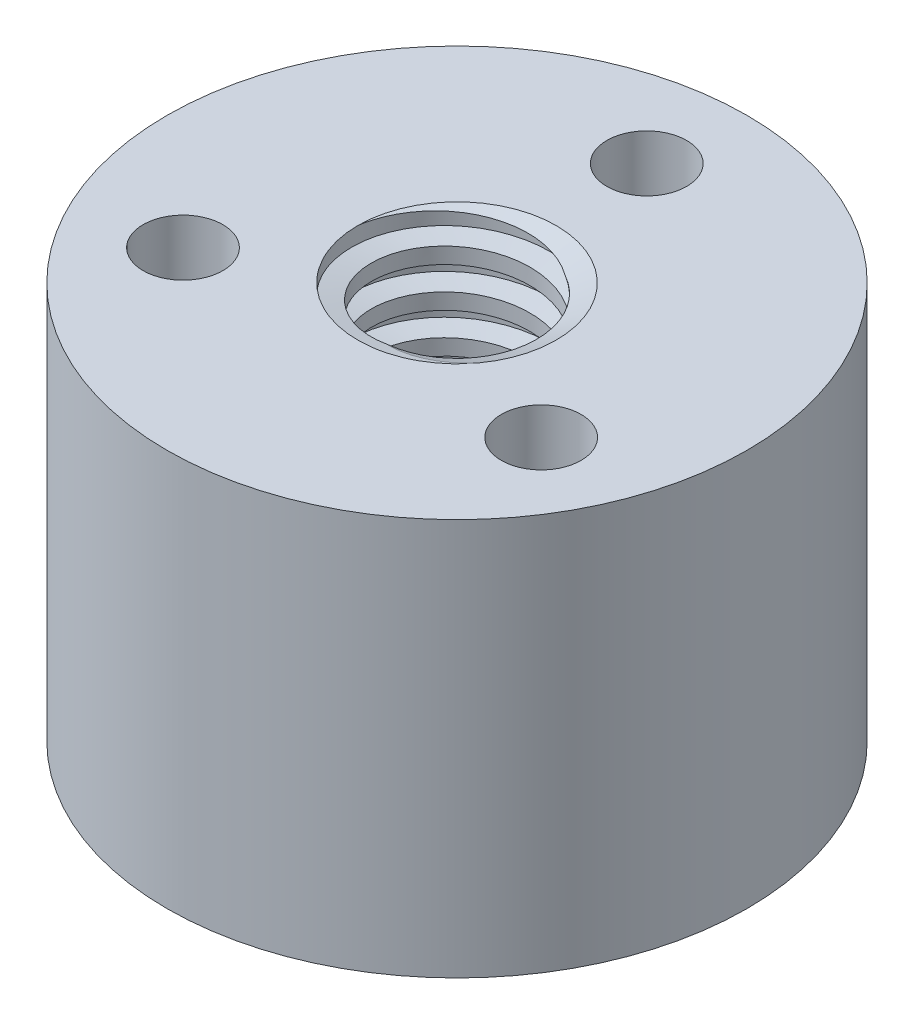
SolidWorks part; units mm, degrees
note: '?' marks a value the reader was unsure of.
ref_plane "Front Plane" through (0, 0, 0) normal (0, 0, 1) x (1, 0, 0)
ref_plane "Top Plane" through (0, 0, 0) normal (0, 1, 0) x (1, 0, 0)
ref_plane "Right Plane" through (0, 0, 0) normal (1, 0, 0) x (0, 0, -1)
sketch "Sketch1" plane through (0, 0, 0) normal (0, 1, 0) x (1, 0, 0)
  circle A0 centre (0, 0) radius 18.561
  circle A1 centre (0, 0) radius 5.0927
  dimension "D1" = 10.1854
  dimension "D2" = 37.1221
extrude "Boss-Extrude1" add sketch "Sketch1" along normal blind 25.4
ref_axis "Axis1" through (0, 25.4, 0) along (0, -1, 0)?
ref_plane "Plane1" through (0, 30.48, 0) normal (0, 1, 0) x (-1, 0, 0)
sketch "Sketch8" plane through (0, 30.48, 0) normal (0, 1, 0) x (-1, 0, 0)
  circle A0 centre (0, 0) radius 6.35
  dimension "D1" = 12.7
curve "Helix/Spiral3" pitch 2.54 height 38.1 turns 15
sketch "Sketch9" plane through (0, 0, 0) normal (1, 0, 0) x (0, 0, -1)
  line L0 (6.35, 29.845) -> (6.35, 28.829)
  line L1 (6.35, 28.829) -> (5.08, 28.575)
  line L2 (5.08, 28.575) -> (5.08, 30.099)
  line L3 (5.08, 30.099) -> (6.35, 29.845)
  spline S2 degree 3 poles (0, 30.48) (0.8259, 30.4274) (2.4957, 30.3211) (4.6064, 30.1625) (6.0195, 30.0037) (6.5153, 29.845) (6.0194, 29.6862) (4.607, 29.5275) (2.4933, 29.3687) (0, 29.21) (-2.4933, 29.0512) (-4.607, 28.8925) (-6.0194, 28.7337) (-6.5153, 28.575) (-6.0194, 28.4162) (-4.607, 28.2575) (-2.4933, 28.0987) (0, 27.94) (2.4933, 27.7812) (4.607, 27.6225) (6.0194, 27.4637) (6.5153, 27.305) (6.0194, 27.1462) (4.607, 26.9875) (2.4933, 26.8287) (0, 26.67) (-2.4933, 26.5113) (-4.607, 26.3525) (-6.0194, 26.1938) (-6.5153, 26.035) (-6.0194, 25.8762) (-4.607, 25.7175) (-2.4933, 25.5587) (0, 25.4) (2.4933, 25.2412) (4.607, 25.0825) (6.0194, 24.9238) (6.5153, 24.765) (6.0194, 24.6062) (4.607, 24.4475) (2.4933, 24.2887) (0, 24.13) (-2.4933, 23.9712) (-4.607, 23.8125) (-6.0194, 23.6537) (-6.5153, 23.495) (-6.0194, 23.3362) (-4.607, 23.1775) (-2.4933, 23.0188) (0, 22.86) (2.4933, 22.7013) (4.607, 22.5425) (6.0194, 22.3837) (6.5153, 22.225) (6.0194, 22.0663) (4.607, 21.9075) (2.4933, 21.7488) (0, 21.59) (-2.4933, 21.4313) (-4.607, 21.2725) (-6.0194, 21.1138) (-6.5153, 20.955) (-6.0194, 20.7963) (-4.607, 20.6375) (-2.4933, 20.4788) (0, 20.32) (2.4933, 20.1613) (4.607, 20.0025) (6.0194, 19.8438) (6.5153, 19.685) (6.0194, 19.5263) (4.607, 19.3675) (2.4933, 19.2088) (0, 19.05) (-2.4933, 18.8913) (-4.607, 18.7325) (-6.0194, 18.5738) (-6.5153, 18.415) (-6.0194, 18.2563) (-4.607, 18.0975) (-2.4933, 17.9388) (0, 17.78) (2.4933, 17.6213) (4.607, 17.4625) (6.0194, 17.3038) (6.5153, 17.145) (6.0194, 16.9863) (4.607, 16.8275) (2.4933, 16.6688) (0, 16.51) (-2.4933, 16.3513) (-4.607, 16.1925) (-6.0194, 16.0338) (-6.5153, 15.875) (-6.0194, 15.7163) (-4.607, 15.5575) (-2.4933, 15.3988) (0, 15.24) (2.4933, 15.0813) (4.607, 14.9225) (6.0194, 14.7638) (6.5153, 14.605) (6.0194, 14.4463) (4.607, 14.2875) (2.4933, 14.1288) (0, 13.97) (-2.4933, 13.8113) (-4.607, 13.6525) (-6.0194, 13.4938) (-6.5153, 13.335) (-6.0194, 13.1763) (-4.607, 13.0175) (-2.4933, 12.8588) (0, 12.7) (2.4933, 12.5413) (4.607, 12.3825) (6.0194, 12.2238) (6.5153, 12.065) (6.0194, 11.9063) (4.607, 11.7475) (2.4933, 11.5888) (0, 11.43) (-2.4933, 11.2713) (-4.607, 11.1125) (-6.0194, 10.9538) (-6.5153, 10.795) (-6.0194, 10.6363) (-4.607, 10.4775) (-2.4933, 10.3188) (0, 10.16) (2.4933, 10.0013) (4.607, 9.8425) (6.0194, 9.6838) (6.5153, 9.525) (6.0194, 9.3663) (4.607, 9.2075) (2.4933, 9.0488) (0, 8.89) (-2.4933, 8.7313) (-4.607, 8.5725) (-6.0194, 8.4138) (-6.5153, 8.255) (-6.0194, 8.0963) (-4.607, 7.9375) (-2.4933, 7.7788) (0, 7.62) (2.4933, 7.4613) (4.607, 7.3025) (6.0194, 7.1438) (6.5153, 6.985) (6.0194, 6.8263) (4.607, 6.6675) (2.4933, 6.5088) (0, 6.35) (-2.4933, 6.1913) (-4.607, 6.0325) (-6.0194, 5.8738) (-6.5153, 5.715) (-6.0194, 5.5563) (-4.607, 5.3975) (-2.4933, 5.2388) (0, 5.08) (2.4933, 4.9213) (4.607, 4.7625) (6.0194, 4.6038) (6.5153, 4.445) (6.0194, 4.2863) (4.607, 4.1275) (2.4933, 3.9688) (0, 3.81) (-2.4933, 3.6513) (-4.607, 3.4925) (-6.0194, 3.3338) (-6.5153, 3.175) (-6.0194, 3.0163) (-4.607, 2.8575) (-2.4933, 2.6988) (0, 2.54) (2.4933, 2.3813) (4.607, 2.2225) (6.0194, 2.0638) (6.5153, 1.905) (6.0194, 1.7463) (4.607, 1.5875) (2.4933, 1.4288) (0, 1.27) (-2.4933, 1.1113) (-4.607, 0.9525) (-6.0194, 0.7938) (-6.5153, 0.635) (-6.0194, 0.4763) (-4.607, 0.3175) (-2.4933, 0.1588) (0, 0) (2.4933, -0.1587) (4.607, -0.3175) (6.0194, -0.4762) (6.5153, -0.635) (6.0194, -0.7937) (4.607, -0.9525) (2.4933, -1.1112) (0, -1.27) (-2.4933, -1.4287) (-4.607, -1.5875) (-6.0194, -1.7462) (-6.5153, -1.905) (-6.0194, -2.0637) (-4.607, -2.2225) (-2.4933, -2.3812) (0, -2.54) (2.4933, -2.6987) (4.607, -2.8575) (6.0194, -3.0162) (6.5153, -3.175) (6.0194, -3.3337) (4.607, -3.4925) (2.4933, -3.6512) (0, -3.81) (-2.4933, -3.9687) (-4.607, -4.1275) (-6.0194, -4.2862) (-6.5153, -4.445) (-6.0194, -4.6037) (-4.607, -4.7625) (-2.4933, -4.9212) (0, -5.08) (2.4933, -5.2387) (4.607, -5.3975) (6.0194, -5.5562) (6.5153, -5.715) (6.0194, -5.8737) (4.607, -6.0325) (2.4933, -6.1912) (0, -6.35) (-2.4933, -6.5087) (-4.607, -6.6675) (-6.0194, -6.8262) (-6.5153, -6.985) (-6.0195, -7.1437) (-4.6064, -7.3025) (-2.4957, -7.4611) (-0.8259, -7.5674) (0, -7.62) knots 0 0 0 0 0.004167 0.008333 0.0125 0.016667 0.020833 0.025 0.029167 0.033333 0.0375 0.041667 0.045833 0.05 0.054167 0.058333 0.0625 0.066667 0.070833 0.075 0.079167 0.083333 0.0875 0.091667 0.095833 0.1 0.104167 0.108333 0.1125 0.116667 0.120833 0.125 0.129167 0.133333 0.1375 0.141667 0.145833 0.15 0.154167 0.158333 0.1625 0.166667 0.170833 0.175 0.179167 0.183333 0.1875 0.191667 0.195833 0.2 0.204167 0.208333 0.2125 0.216667 0.220833 0.225 0.229167 0.233333 0.2375 0.241667 0.245833 0.25 0.254167 0.258333 0.2625 0.266667 0.270833 0.275 0.279167 0.283333 0.2875 0.291667 0.295833 0.3 0.304167 0.308333 0.3125 0.316667 0.320833 0.325 0.329167 0.333333 0.3375 0.341667 0.345833 0.35 0.354167 0.358333 0.3625 0.366667 0.370833 0.375 0.379167 0.383333 0.3875 0.391667 0.395833 0.4 0.404167 0.408333 0.4125 0.416667 0.420833 0.425 0.429167 0.433333 0.4375 0.441667 0.445833 0.45 0.454167 0.458333 0.4625 0.466667 0.470833 0.475 0.479167 0.483333 0.4875 0.491667 0.495833 0.5 0.504167 0.508333 0.5125 0.516667 0.520833 0.525 0.529167 0.533333 0.5375 0.541667 0.545833 0.55 0.554167 0.558333 0.5625 0.566667 0.570833 0.575 0.579167 0.583333 0.5875 0.591667 0.595833 0.6 0.604167 0.608333 0.6125 0.616667 0.620833 0.625 0.629167 0.633333 0.6375 0.641667 0.645833 0.65 0.654167 0.658333 0.6625 0.666667 0.670833 0.675 0.679167 0.683333 0.6875 0.691667 0.695833 0.7 0.704167 0.708333 0.7125 0.716667 0.720833 0.725 0.729167 0.733333 0.7375 0.741667 0.745833 0.75 0.754167 0.758333 0.7625 0.766667 0.770833 0.775 0.779167 0.783333 0.7875 0.791667 0.795833 0.8 0.804167 0.808333 0.8125 0.816667 0.820833 0.825 0.829167 0.833333 0.8375 0.841667 0.845833 0.85 0.854167 0.858333 0.8625 0.866667 0.870833 0.875 0.879167 0.883333 0.8875 0.891667 0.895833 0.9 0.904167 0.908333 0.9125 0.916667 0.920833 0.925 0.929167 0.933333 0.9375 0.941667 0.945833 0.95 0.954167 0.958333 0.9625 0.966667 0.970833 0.975 0.979167 0.983333 0.9875 0.991667 0.995833 1 1 1 1 construction
  dimension "D1" = 1.27
  dimension "D2" = 1.524
  dimension "D3" = 1.016
sweep "Cut-Sweep2" cut profiles "Sketch9" path "Helix/Spiral3"
sketch "Sketch12" plane through (0, 0, 0) normal (0, 0, 1) x (1, 0, 0)
  line L0 (0, 22.4389) -> (6.35, 25.4)
  line L1 (0, 25.4) -> (0, 0) construction
  line L2 (18.561, 25.4) -> (-18.561, 25.4) construction
  line L3 (6.35, 25.4) -> (0, 25.4)
  line L4 (0, 25.4) -> (0, 22.4389)
  line L5 (0, 18.5161) -> (0, 33.0505) construction
  line L6 (0, 0) -> (6.35, 0)
  line L7 (-18.561, 0) -> (18.561, 0) construction
  line L8 (6.35, 0) -> (0, 2.9611)
  line L9 (0, 2.9611) -> (0, 0)
  dimension "D1" = 6.35
  dimension "D2" = 25
  dimension "D3" = 6.35
  dimension "D4" = 25
revolve "Cut-Revolve2" cut sketch "Sketch12" angle 360 about L5
hole_wizard "1/4-20 Tapped Hole1" positions "Sketch14" profile "Sketch13" tap size "1/4-20" standard "Ansi Inch"
sketch "Sketch14" plane through (0, 25.4, 0) normal (0, 1, 0) x (-1, 0, 0)
  circle A0 centre (0, 0) radius 12.7
  point P0 (0.5461, -12.6883)
  point P21 (-11.2599, 5.8721)
  point P22 (10.7168, 6.8162)
  dimension "D1" = 25.4
  dimension "D3" = 12.7
  dimension "D2" = 3
sketch "Sketch13" plane through (-0.5461, 25.4, -12.6883) normal (1, 0, 0) x (0, 0, 1)
  line L0 (0, 0) -> (0, 23.1238)
  line L1 (0, 23.1238) -> (2.5527, 21.59)
  line L2 (2.5527, 21.59) -> (2.5527, 0)
  line L5 (2.5527, 0) -> (0, 0)
  line L10 (0, 23.1238) -> (-2.5527, 21.59) construction
  line L11 (0, -6.35) -> (0, 107.95) construction
  dimension "Tap Drill Dia." = 5.1054
  dimension "Tap Drill Depth" = 21.59
  dimension "Drill Angle" = 118
cosmetic thread "Hole Thread1" parameters "D1"=17.78, "D2"=6.35
cosmetic thread "Hole Thread2" parameters "D1"=17.78, "D2"=6.35
cosmetic thread "Hole Thread3" parameters "D1"=17.78, "D2"=6.35
